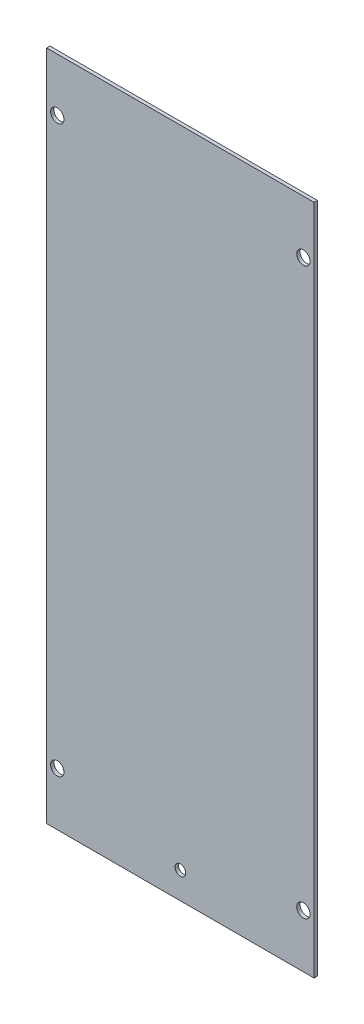
SolidWorks part; units mm, degrees
material "6061 Alloy"
ref_plane "Front" through (0, 0, 0) normal (0, 0, 1) x (1, 0, 0)
ref_plane "Top" through (0, 0, 0) normal (0, 1, 0) x (1, 0, 0)
ref_plane "Right" through (0, 0, 0) normal (1, 0, 0) x (0, 0, -1)
sketch "Sketch1" plane through (0, 0, 0) normal (0, 0, 1) x (1, 0, 0)
  line L1 (0, 0) -> (127.635, 0)
  line L2 (0, 0) -> (0, 320.675)
  line L3 (0, 320.675) -> (127.635, 320.675)
  line L4 (127.635, 0) -> (127.635, 320.675)
  dimension "D1" = 320.675
  dimension "D2" = 127.635
extrude "Main Plate" add sketch "Sketch1" along normal blind 1.5875
sketch "Sketch2" plane through (0, 0, 1.5875) normal (0, 0, 1) x (1, 0, 0)
  line L0 (0, 320.675) -> (0, 0) construction
  line L1 (127.635, 320.675) -> (0, 320.675) construction
  circle A0 centre (5.08, 295.275) radius 3.175
  dimension "D3" = 6.35
  dimension "D1" = 5.08
  dimension "D2" = 25.4
extrude "Bolt Holes" cut sketch "Sketch2" against normal blind 6.35
pattern_linear "LPattern1" count 2 spacing 117.475 along (1, 0, 0) count 2 spacing 269.875 along (0, -1, 0) of "Bolt Holes"
sketch "Sketch3" plane through (0, 0, 1.5875) normal (0, 0, 1) x (1, 0, 0)
  line L0 (0, 320.675) -> (0, 0) construction
  line L1 (0, 0) -> (127.635, 0) construction
  circle A0 centre (63.8175, 12.7) radius 2.54
  dimension "D1" = 5.08
  dimension "D2" = 63.8175
  dimension "D3" = 12.7
extrude "Wire Hole" cut sketch "Sketch3" against normal blind 6.35
